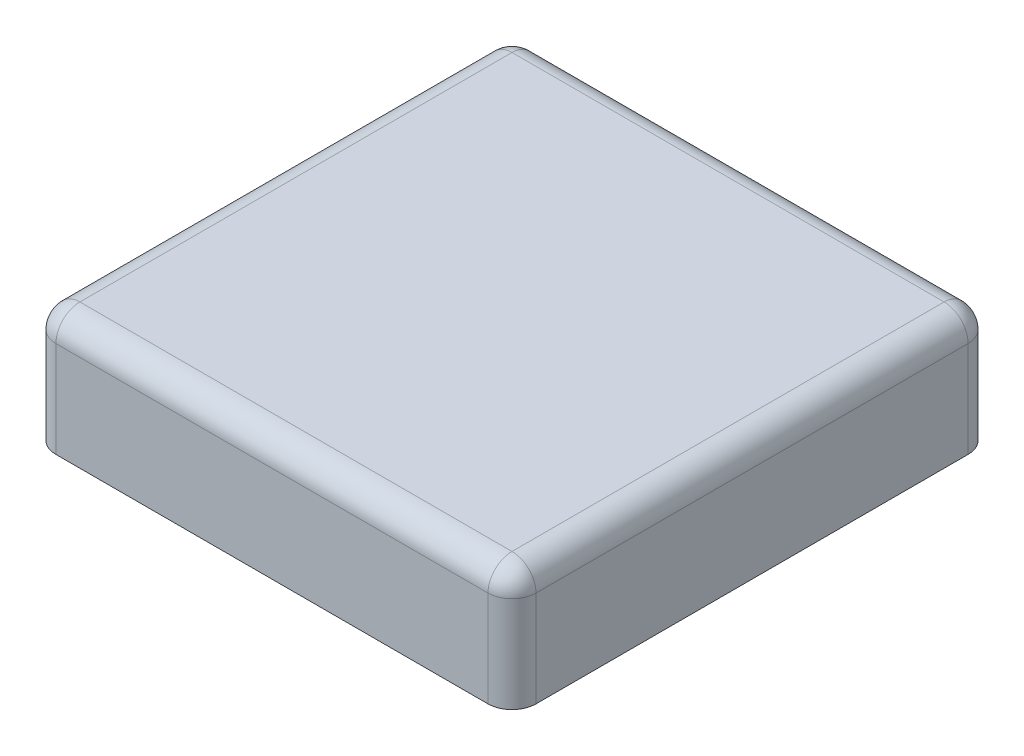
SolidWorks part; units mm, degrees
ref_plane "Front Plane" through (0, 0, 0) normal (0, 0, 1) x (1, 0, 0)
ref_plane "Top Plane" through (0, 0, 0) normal (0, 1, 0) x (1, 0, 0)
ref_plane "Right Plane" through (0, 0, 0) normal (1, 0, 0) x (0, 0, -1)
sketch "Sketch1" plane through (0, 0, 0) normal (0, 1, 0) x (1, 0, 0)
  line L1 (-30, -30) -> (30, -30)
  line L2 (-30, -30) -> (-30, 30)
  line L3 (-30, 30) -> (30, 30)
  line L4 (30, -30) -> (30, 30)
  line L5 (-30, -30) -> (30, 30) construction
  line L6 (-30, 30) -> (30, -30) construction
  point P0 (0, 0)
  dimension "D1" = 60
  dimension "D2" = 60
extrude "Boss-Extrude1" add sketch "Sketch1" along normal blind 15
fillet "Fillet1" radius 3 8 edges at (0, 15, 30) (-30, 15, 0) (0, 15, -30) (30, 15, 0) (30, 7.5, -30) (30, 7.5, 30) (-30, 7.5, 30) (-30, 7.5, -30)
shell "Shell1" thickness 3 removed face at (0, 0, 0)
